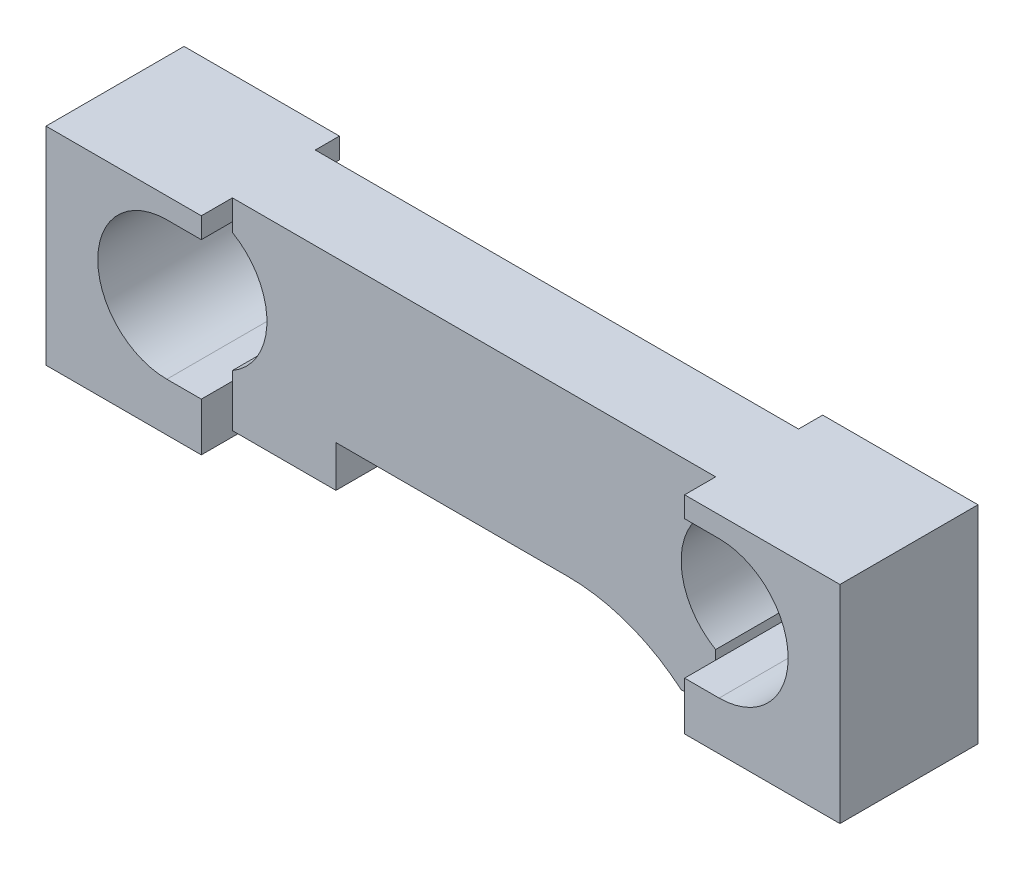
SolidWorks part; units mm, degrees
material "6061-T6 (SS)"
ref_plane "Front Plane" through (0, 0, 0) normal (0, 0, 1) x (1, 0, 0)
ref_plane "Top Plane" through (0, 0, 0) normal (0, 1, 0) x (1, 0, 0)
ref_plane "Right Plane" through (0, 0, 0) normal (1, 0, 0) x (0, 0, -1)
sketch "Sketch1" plane through (0, 0, 0) normal (0, 1, 0) x (1, 0, 0)
  line L1 (0, 0) -> (292.1, 0)
  line L2 (0, 0) -> (0, 50.8)
  line L3 (0, 50.8) -> (292.1, 50.8)
  line L4 (292.1, 0) -> (292.1, 50.8)
  dimension "D1" = 50.8
  dimension "D2" = 292.1
extrude "Boss-Extrude1" add sketch "Sketch1" along normal blind 76.2
sketch "Sketch2" plane through (0, 0, 0) normal (0, -1, 0) x (1, 0, 0)
  line L0 (0, 0) -> (292.1, 0) construction
  line L1 (57.15, 0) -> (234.95, 0)
  line L2 (57.15, 0) -> (57.15, -11.43)
  line L3 (57.15, -11.43) -> (234.95, -11.43)
  line L4 (234.95, 0) -> (234.95, -11.43)
  line L5 (292.1, -50.8) -> (0, -50.8) construction
  line L6 (57.15, -50.8) -> (234.95, -50.8)
  line L7 (57.15, -50.8) -> (57.15, -41.91)
  line L8 (57.15, -41.91) -> (234.95, -41.91)
  line L9 (234.95, -50.8) -> (234.95, -41.91)
  line L10 (292.1, 0) -> (292.1, -50.8) construction
  line L11 (0, -50.8) -> (0, 0) construction
  point P14 (292.1, -25.4)
  dimension "D1" = 11.43
  dimension "D2" = 30.48
  dimension "D3" = 57.15
  dimension "D4" = 57.15
  dimension "D5" = 57.15
  dimension "D6" = 177.8
extrude "Cut-Extrude1" cut sketch "Sketch2" against normal through all
sketch "Sketch3" plane through (0, 0, 0) normal (0, -1, 0) x (1, 0, 0)
  line L1 (57.15, -11.43) -> (234.95, -11.43)
  line L2 (57.15, -11.43) -> (57.15, -41.91)
  line L3 (57.15, -41.91) -> (234.95, -41.91)
  line L4 (234.95, -11.43) -> (234.95, -41.91)
extrude "Cut-Extrude2" cut sketch "Sketch3" against normal blind 2.032
sketch "Sketch4" plane through (0, 2.032, 0) normal (0, -1, 0) x (1, 0, 0)
  line L0 (57.15, -41.91) -> (234.95, -41.91) construction
  line L1 (234.95, -11.43) -> (95.25, -11.43)
  line L2 (234.95, -11.43) -> (234.95, -41.91)
  line L3 (234.95, -41.91) -> (95.25, -41.91)
  line L4 (95.25, -11.43) -> (95.25, -41.91)
  line L5 (57.15, -11.43) -> (57.15, -41.91) construction
  dimension "D1" = 38.1
extrude "Cut-Extrude3" cut sketch "Sketch4" against normal blind 15.24
sketch "Sketch5" plane through (0, 17.272, 0) normal (0, -1, 0) x (1, 0, 0)
  line L0 (234.95, -11.43) -> (95.25, -11.43) construction
  line L1 (222.25, -11.43) -> (234.95, -11.43)
  line L2 (222.25, -11.43) -> (222.25, -41.91)
  line L3 (222.25, -41.91) -> (234.95, -41.91)
  line L4 (234.95, -11.43) -> (234.95, -41.91)
  dimension "D1" = 12.7
extrude "Boss-Extrude2" add sketch "Sketch5" along normal blind 15.24
fillet "Fillet1" radius 64.77 1 edges at (222.25, 17.272, -26.67)
sketch "Sketch6" plane through (0, 0, 0) normal (0, 0, 1) x (1, 0, 0)
  line L0 (0, 76.2) -> (0, 0) construction
  line L1 (0, 0) -> (57.15, 0) construction
  line L2 (44.45, 17.78) -> (57.15, 17.78)
  line L3 (57.15, 76.2) -> (57.15, 0) construction
  line L4 (57.15, 17.78) -> (57.15, 21.183)
  line L5 (44.45, 68.58) -> (57.15, 68.58)
  line L6 (57.15, 68.58) -> (57.15, 65.177)
  arc A0 (57.15, 21.183) -> (57.15, 65.177) centre (44.45, 43.18) ccw
  arc A1 (44.45, 68.58) -> (44.45, 17.78) centre (44.45, 43.18) ccw
  dimension "D1" = 50.8
  dimension "D2" = 44.45
  dimension "D3" = 43.18
extrude "Cut-Extrude4" cut sketch "Sketch6" against normal through all
sketch "Sketch7" plane through (0, 0, 0) normal (0, 0, 1) x (1, 0, 0)
  line L0 (292.1, 76.2) -> (292.1, 0) construction
  line L1 (234.95, 0) -> (292.1, 0) construction
  line L2 (247.65, 17.78) -> (234.95, 17.78)
  line L3 (234.95, 76.2) -> (234.95, 0) construction
  line L4 (234.95, 17.78) -> (234.95, 21.183)
  line L5 (247.65, 68.58) -> (234.95, 68.58)
  line L6 (234.95, 68.58) -> (234.95, 65.177)
  arc A0 (234.95, 65.177) -> (234.95, 21.183) centre (247.65, 43.18) ccw
  arc A1 (247.65, 17.78) -> (247.65, 68.58) centre (247.65, 43.18) ccw
  dimension "D1" = 50.8
  dimension "D2" = 44.45
  dimension "D3" = 43.18
extrude "Cut-Extrude5" cut sketch "Sketch7" against normal through all
